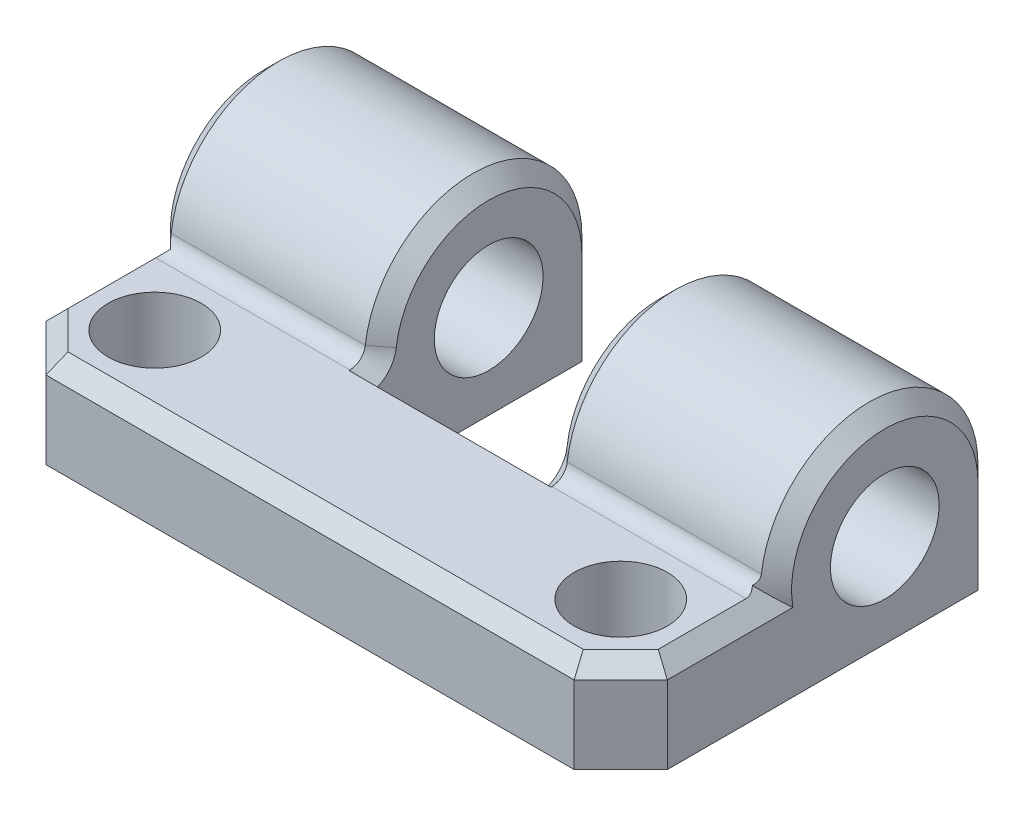
SolidWorks part; units mm, degrees
ref_plane "Vorne" through (0, 0, 0) normal (0, 0, 1) x (1, 0, 0)
ref_plane "Oben" through (0, 0, 0) normal (0, 1, 0) x (1, 0, 0)
ref_plane "Rechts" through (0, 0, 0) normal (1, 0, 0) x (0, 0, -1)
sketch "Skizze1" plane through (0, 0, 0) normal (0, 1, 0) x (1, 0, 0)
  line L1 (10, 6) -> (-10, 6)
  line L2 (10, 6) -> (10, -6)
  line L3 (10, -6) -> (-10, -6)
  line L4 (-10, 6) -> (-10, -6)
  line L5 (10, 6) -> (-10, -6) construction
  line L6 (10, -6) -> (-10, 6) construction
  point P0 (0, 0)
  dimension "D1" = 12
  dimension "D2" = 20
extrude "Aufsatz-Linear austragen1" add sketch "Skizze1" along normal blind 3
sketch "Skizze2" plane through (0, 3, 0) normal (0, 1, 0) x (1, 0, 0)
  line L0 (-10, 6) -> (-10, -6) construction
  line L1 (-10, -6) -> (10, -6) construction
  line L2 (0, -55) -> (0, 55) construction
  circle A0 centre (-7.5, -3.5) radius 1.5
  circle A1 centre (7.5, -3.5) radius 1.5
  dimension "D1" = 3
  dimension "D2" = 2.5
  dimension "D3" = 2.5
extrude "Schnitt-Linear austragen1" cut sketch "Skizze2" against normal up to next
sketch "Skizze3" plane through (-10, 0, 0) normal (-1, 0, 0) x (0, 0, 1)
  line L0 (-6, 3) -> (6, 3) construction
  line L1 (-6, 3) -> (1, 3)
  arc A0 (1, 3) -> (-6, 3) centre (-2.5, 3) ccw
  dimension "D1" = 7
  dimension "D2" = 2.5
  dimension "D3" = 0
extrude "Aufsatz-Linear austragen2" add sketch "Skizze3" against normal up to vertex (20 mm away) contours A0 L1 up to point (10, 3, -6)
chamfer "Fase1" distance 1.5 angle 45 2 edges at (10, 1.5, 6) (-10, 1.5, 6)
sketch "Skizze4" plane through (-10, 0, 0) normal (-1, 0, 0) x (0, 0, 1)
  circle A0 centre (-2.5, 3) radius 1.75
  arc A1 (1, 3) -> (-6, 3) centre (-2.5, 3) ccw construction
  dimension "D1" = 3.5
extrude "Schnitt-Linear austragen2" cut sketch "Skizze4" against normal through all
sketch "Skizze5" plane through (0, 0, 0) normal (0, 1, 0) x (1, 0, 0)
  line L1 (-2.75, 6) -> (2.75, 6)
  line L2 (-2.75, 6) -> (-2.75, -1)
  line L3 (-2.75, -1) -> (2.75, -1)
  line L4 (2.75, 6) -> (2.75, -1)
  line L5 (-2.75, 6) -> (2.75, -1) construction
  line L6 (-2.75, -1) -> (2.75, 6) construction
  line L8 (10, 6) -> (-10, 6) construction
  point P0 (0, 2.5)
  dimension "D1" = 5.5
  dimension "D2" = 7
  dimension "D3" = 3.5
extrude "Schnitt-Linear austragen5" cut sketch "Skizze5" along normal through all
chamfer "Fase4" distance 0.5 angle 45 10 edges at (0, 3, 1) (-10, 1.5, -6) (10, 1.5, -6) (-10, 6.5, -2.5) (10, 6.5, -2.5) (10, 3, 2.75) (9.25, 3, 5.25) (0, 3, 6) (-9.25, 3, 5.25) (-10, 3, 2.75)
fillet "Verrundung3" radius 0.5 2 edges at (6.125, 3, 1) (-6.125, 3, 1)
chamfer "Fase6" distance 0.5 angle 45 8 edges at (2.75, 3, 1.4843) (2.75, 1.5, -6) (2.75, 3.125, 1.1379) (2.75, 6.4931, -2.7192) (-2.75, 3, 1.4843) (-2.75, 3.125, 1.1379) (-2.75, 1.5, -6) (-2.75, 6.4931, -2.7192)
